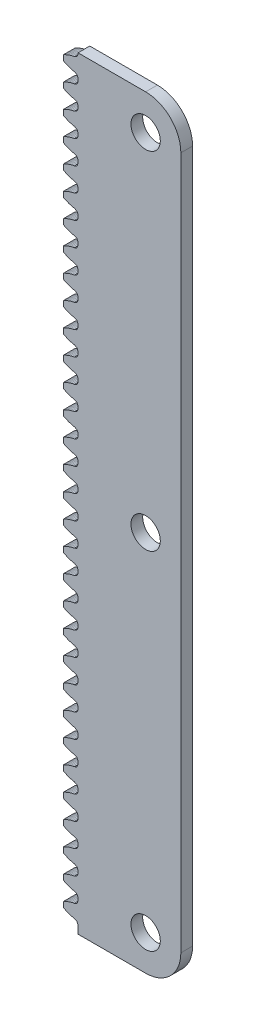
SolidWorks part; units mm, degrees
ref_plane "Спереди" through (0, 0, 0) normal (0, 0, 1) x (1, 0, 0)
ref_plane "Сверху" through (0, 0, 0) normal (0, 1, 0) x (1, 0, 0)
ref_plane "Справа" through (0, 0, 0) normal (1, 0, 0) x (0, 0, -1)
sketch "Эскиз1" plane through (0, 0, 0) normal (0, 0, 1) x (1, 0, 0)
  line L1 (-17.5787, 49.8917) -> (2.4213, 49.8917)
  line L2 (-17.5787, 49.8917) -> (-17.5787, -80.1083)
  line L3 (-17.5787, -80.1083) -> (2.4213, -80.1083)
  line L4 (2.4213, 49.8917) -> (2.4213, -80.1083)
  dimension "D1" = 130
  dimension "D2" = 20
sheet metal parameters "Листовой металл1" thickness 2 parameters "D1"=1.1, "Толщина"=2
base flange "Базовая кромка1" sketch "Эскиз1" thickness 2 reverse thickness direction no parameters "D1"=1.1
fillet "Скругление1" radius 6 2 edges at (2.4213, -80.1083, -1) (2.4213, 49.8917, -1)
sketch "Эскиз4" plane through (0, 0, 0) normal (0, 0, 1) x (1, 0, 0)
  line L0 (-3.5787, 43.8917) -> (-3.5787, -74.1083) construction
  line L1 (-17.5787, -15.1083) -> (2.4213, -15.1083) construction
  line L2 (-17.5787, 49.8917) -> (-17.5787, -80.1083) construction
  line L3 (2.4213, -74.1083) -> (2.4213, 43.8917) construction
  circle A0 centre (-3.5787, -15.1083) radius 2.5
  circle A1 centre (-3.5787, 43.8917) radius 2.5
  circle A2 centre (-3.5787, -74.1083) radius 2.5
  dimension "D1" = 5
  dimension "D2" = 5
  dimension "D3" = 5
extrude "Вырез-Вытянуть1" cut sketch "Эскиз4" against normal blind 10 normal cut yes
sketch "Эскиз5" plane through (0, 0, -2) normal (0, 0, -1) x (-1, 0, 0)
  line L0 (15.1379, 49.5364) -> (15.2757, 49.235)
  line L1 (15.2757, 49.235) -> (15.7076, 49.0269)
  line L2 (15.7076, 49.0269) -> (16.0187, 48.968)
  line L3 (16.0187, 48.968) -> (16.3309, 48.8851)
  line L4 (16.3309, 48.8851) -> (16.6436, 48.7814)
  line L5 (16.6436, 48.7814) -> (16.9562, 48.6588)
  line L6 (16.9562, 48.6588) -> (17.2684, 48.5186)
  line L7 (17.2684, 48.5186) -> (17.5796, 48.3616)
  line L8 (17.5796, 48.3616) -> (17.5796, 47.4619)
  line L9 (17.5796, 47.4619) -> (17.2684, 47.3049)
  line L10 (17.2684, 47.3049) -> (16.9562, 47.1647)
  line L11 (16.9562, 47.1647) -> (16.6436, 47.0421)
  line L12 (16.6436, 47.0421) -> (16.3309, 46.9384)
  line L13 (16.3309, 46.9384) -> (16.0187, 46.8555)
  line L14 (16.0187, 46.8555) -> (15.7076, 46.7967)
  line L15 (15.7076, 46.7967) -> (15.2757, 46.5886)
  line L16 (15.2757, 46.5886) -> (15.1379, 46.2872)
  line L17 (15.1379, 46.2872) -> (15.0887, 45.8974)
  line L18 (15.1379, 45.5076) -> (15.2757, 45.2062)
  line L19 (15.2757, 45.2062) -> (15.7076, 44.9981)
  line L20 (15.7076, 44.9981) -> (16.0187, 44.9393)
  line L21 (16.3309, 44.8564) -> (16.6436, 44.7527)
  line L22 (16.6436, 44.7527) -> (16.9562, 44.6301)
  line L23 (16.9562, 44.6301) -> (17.2684, 44.4899)
  line L24 (17.2684, 44.4899) -> (17.5796, 44.3329)
  line L25 (17.5796, 43.4332) -> (17.2684, 43.2762)
  line L26 (17.2684, 43.2762) -> (16.9562, 43.136)
  line L27 (16.9562, 43.136) -> (16.6436, 43.0134)
  line L28 (16.6436, 43.0134) -> (16.3309, 42.9097)
  line L29 (16.3309, 42.9097) -> (16.0187, 42.8268)
  line L30 (16.0187, 42.8268) -> (15.7076, 42.7679)
  line L31 (15.7076, 42.7679) -> (15.2757, 42.5599)
  line L32 (15.2757, 42.5599) -> (15.1379, 42.2584)
  line L33 (15.1379, 42.2584) -> (15.0887, 41.8687)
  line L34 (15.0887, 45.8974) -> (15.1379, 45.5076)
  line L35 (16.0187, 44.9393) -> (16.3309, 44.8564)
  line L36 (17.5796, 44.3329) -> (17.5796, 43.4332)
  line L37 (15.1379, 41.4789) -> (15.2757, 41.1775)
  line L38 (15.2757, 41.1775) -> (15.7076, 40.9694)
  line L39 (15.7076, 40.9694) -> (16.0187, 40.9106)
  line L40 (16.3309, 40.8276) -> (16.6436, 40.7239)
  line L41 (16.6436, 40.7239) -> (16.9562, 40.6014)
  line L42 (16.9562, 40.6014) -> (17.2684, 40.4611)
  line L43 (17.2684, 40.4611) -> (17.5796, 40.3041)
  line L44 (17.5796, 39.4045) -> (17.2684, 39.2475)
  line L45 (17.2684, 39.2475) -> (16.9562, 39.1072)
  line L46 (16.9562, 39.1072) -> (16.6436, 38.9847)
  line L47 (16.6436, 38.9847) -> (16.3309, 38.881)
  line L48 (16.3309, 38.881) -> (16.0187, 38.798)
  line L49 (16.0187, 38.798) -> (15.7076, 38.7392)
  line L50 (15.7076, 38.7392) -> (15.2757, 38.5311)
  line L51 (15.2757, 38.5311) -> (15.1379, 38.2297)
  line L52 (15.1379, 38.2297) -> (15.0887, 37.8399)
  line L53 (15.0887, 41.8687) -> (15.1379, 41.4789)
  line L54 (16.0187, 40.9106) -> (16.3309, 40.8276)
  line L55 (17.5796, 40.3041) -> (17.5796, 39.4045)
  line L56 (15.1379, 37.4502) -> (15.2757, 37.1488)
  line L57 (15.2757, 37.1488) -> (15.7076, 36.9407)
  line L58 (15.7076, 36.9407) -> (16.0187, 36.8818)
  line L59 (16.3309, 36.7989) -> (16.6436, 36.6952)
  line L60 (16.6436, 36.6952) -> (16.9562, 36.5726)
  line L61 (16.9562, 36.5726) -> (17.2684, 36.4324)
  line L62 (17.2684, 36.4324) -> (17.5796, 36.2754)
  line L63 (17.5796, 35.3757) -> (17.2684, 35.2187)
  line L64 (17.2684, 35.2187) -> (16.9562, 35.0785)
  line L65 (16.9562, 35.0785) -> (16.6436, 34.9559)
  line L66 (16.6436, 34.9559) -> (16.3309, 34.8522)
  line L67 (16.3309, 34.8522) -> (16.0187, 34.7693)
  line L68 (16.0187, 34.7693) -> (15.7076, 34.7105)
  line L69 (15.7076, 34.7105) -> (15.2757, 34.5024)
  line L70 (15.2757, 34.5024) -> (15.1379, 34.201)
  line L71 (15.1379, 34.201) -> (15.0887, 33.8112)
  line L72 (15.0887, 37.8399) -> (15.1379, 37.4502)
  line L73 (16.0187, 36.8818) -> (16.3309, 36.7989)
  line L74 (17.5796, 36.2754) -> (17.5796, 35.3757)
  line L75 (15.1379, 33.4214) -> (15.2757, 33.12)
  line L76 (15.2757, 33.12) -> (15.7076, 32.9119)
  line L77 (15.7076, 32.9119) -> (16.0187, 32.8531)
  line L78 (16.3309, 32.7702) -> (16.6436, 32.6665)
  line L79 (16.6436, 32.6665) -> (16.9562, 32.5439)
  line L80 (16.9562, 32.5439) -> (17.2684, 32.4037)
  line L81 (17.2684, 32.4037) -> (17.5796, 32.2467)
  line L82 (17.5796, 31.347) -> (17.2684, 31.19)
  line L83 (17.2684, 31.19) -> (16.9562, 31.0498)
  line L84 (16.9562, 31.0498) -> (16.6436, 30.9272)
  line L85 (16.6436, 30.9272) -> (16.3309, 30.8235)
  line L86 (16.3309, 30.8235) -> (16.0187, 30.7406)
  line L87 (16.0187, 30.7406) -> (15.7076, 30.6817)
  line L88 (15.7076, 30.6817) -> (15.2757, 30.4736)
  line L89 (15.2757, 30.4736) -> (15.1379, 30.1722)
  line L90 (15.1379, 30.1722) -> (15.0887, 29.7825)
  line L91 (15.0887, 33.8112) -> (15.1379, 33.4214)
  line L92 (16.0187, 32.8531) -> (16.3309, 32.7702)
  line L93 (17.5796, 32.2467) -> (17.5796, 31.347)
  line L94 (15.1379, 29.3927) -> (15.2757, 29.0913)
  line L95 (15.2757, 29.0913) -> (15.7076, 28.8832)
  line L96 (15.7076, 28.8832) -> (16.0187, 28.8244)
  line L97 (16.3309, 28.7414) -> (16.6436, 28.6377)
  line L98 (16.6436, 28.6377) -> (16.9562, 28.5152)
  line L99 (16.9562, 28.5152) -> (17.2684, 28.3749)
  line L100 (17.2684, 28.3749) -> (17.5796, 28.2179)
  line L101 (17.5796, 27.3183) -> (17.2684, 27.1613)
  line L102 (17.2684, 27.1613) -> (16.9562, 27.021)
  line L103 (16.9562, 27.021) -> (16.6436, 26.8985)
  line L104 (16.6436, 26.8985) -> (16.3309, 26.7948)
  line L105 (16.3309, 26.7948) -> (16.0187, 26.7118)
  line L106 (16.0187, 26.7118) -> (15.7076, 26.653)
  line L107 (15.7076, 26.653) -> (15.2757, 26.4449)
  line L108 (15.2757, 26.4449) -> (15.1379, 26.1435)
  line L109 (15.1379, 26.1435) -> (15.0887, 25.7537)
  line L110 (15.0887, 29.7825) -> (15.1379, 29.3927)
  line L111 (16.0187, 28.8244) -> (16.3309, 28.7414)
  line L112 (17.5796, 28.2179) -> (17.5796, 27.3183)
  line L113 (15.1379, 25.364) -> (15.2757, 25.0625)
  line L114 (15.2757, 25.0625) -> (15.7076, 24.8545)
  line L115 (15.7076, 24.8545) -> (16.0187, 24.7956)
  line L116 (16.3309, 24.7127) -> (16.6436, 24.609)
  line L117 (16.6436, 24.609) -> (16.9562, 24.4864)
  line L118 (16.9562, 24.4864) -> (17.2684, 24.3462)
  line L119 (17.2684, 24.3462) -> (17.5796, 24.1892)
  line L120 (17.5796, 23.2895) -> (17.2684, 23.1325)
  line L121 (17.2684, 23.1325) -> (16.9562, 22.9923)
  line L122 (16.9562, 22.9923) -> (16.6436, 22.8697)
  line L123 (16.6436, 22.8697) -> (16.3309, 22.766)
  line L124 (16.3309, 22.766) -> (16.0187, 22.6831)
  line L125 (16.0187, 22.6831) -> (15.7076, 22.6243)
  line L126 (15.7076, 22.6243) -> (15.2757, 22.4162)
  line L127 (15.2757, 22.4162) -> (15.1379, 22.1148)
  line L128 (15.1379, 22.1148) -> (15.0887, 21.725)
  line L129 (15.0887, 25.7537) -> (15.1379, 25.364)
  line L130 (16.0187, 24.7956) -> (16.3309, 24.7127)
  line L131 (17.5796, 24.1892) -> (17.5796, 23.2895)
  line L132 (15.1379, 21.3352) -> (15.2757, 21.0338)
  line L133 (15.2757, 21.0338) -> (15.7076, 20.8257)
  line L134 (15.7076, 20.8257) -> (16.0187, 20.7669)
  line L135 (16.3309, 20.6839) -> (16.6436, 20.5803)
  line L136 (16.6436, 20.5803) -> (16.9562, 20.4577)
  line L137 (16.9562, 20.4577) -> (17.2684, 20.3175)
  line L138 (17.2684, 20.3175) -> (17.5796, 20.1605)
  line L139 (17.5796, 19.2608) -> (17.2684, 19.1038)
  line L140 (17.2684, 19.1038) -> (16.9562, 18.9636)
  line L141 (16.9562, 18.9636) -> (16.6436, 18.841)
  line L142 (16.6436, 18.841) -> (16.3309, 18.7373)
  line L143 (16.3309, 18.7373) -> (16.0187, 18.6544)
  line L144 (16.0187, 18.6544) -> (15.7076, 18.5955)
  line L145 (15.7076, 18.5955) -> (15.2757, 18.3874)
  line L146 (15.2757, 18.3874) -> (15.1379, 18.086)
  line L147 (15.1379, 18.086) -> (15.0887, 17.6963)
  line L148 (15.0887, 21.725) -> (15.1379, 21.3352)
  line L149 (16.0187, 20.7669) -> (16.3309, 20.6839)
  line L150 (17.5796, 20.1605) -> (17.5796, 19.2608)
  line L151 (15.1379, 17.3065) -> (15.2757, 17.0051)
  line L152 (15.2757, 17.0051) -> (15.7076, 16.797)
  line L153 (15.7076, 16.797) -> (16.0187, 16.7381)
  line L154 (16.3309, 16.6552) -> (16.6436, 16.5515)
  line L155 (16.6436, 16.5515) -> (16.9562, 16.429)
  line L156 (16.9562, 16.429) -> (17.2684, 16.2887)
  line L157 (17.2684, 16.2887) -> (17.5796, 16.1317)
  line L158 (17.5796, 15.2321) -> (17.2684, 15.075)
  line L159 (17.2684, 15.075) -> (16.9562, 14.9348)
  line L160 (16.9562, 14.9348) -> (16.6436, 14.8123)
  line L161 (16.6436, 14.8123) -> (16.3309, 14.7086)
  line L162 (16.3309, 14.7086) -> (16.0187, 14.6256)
  line L163 (16.0187, 14.6256) -> (15.7076, 14.5668)
  line L164 (15.7076, 14.5668) -> (15.2757, 14.3587)
  line L165 (15.2757, 14.3587) -> (15.1379, 14.0573)
  line L166 (15.1379, 14.0573) -> (15.0887, 13.6675)
  line L167 (15.0887, 17.6963) -> (15.1379, 17.3065)
  line L168 (16.0187, 16.7381) -> (16.3309, 16.6552)
  line L169 (17.5796, 16.1317) -> (17.5796, 15.2321)
  line L170 (15.1379, 13.2778) -> (15.2757, 12.9763)
  line L171 (15.2757, 12.9763) -> (15.7076, 12.7683)
  line L172 (15.7076, 12.7683) -> (16.0187, 12.7094)
  line L173 (16.3309, 12.6265) -> (16.6436, 12.5228)
  line L174 (16.6436, 12.5228) -> (16.9562, 12.4002)
  line L175 (16.9562, 12.4002) -> (17.2684, 12.26)
  line L176 (17.2684, 12.26) -> (17.5796, 12.103)
  line L177 (17.5796, 11.2033) -> (17.2684, 11.0463)
  line L178 (17.2684, 11.0463) -> (16.9562, 10.9061)
  line L179 (16.9562, 10.9061) -> (16.6436, 10.7835)
  line L180 (16.6436, 10.7835) -> (16.3309, 10.6798)
  line L181 (16.3309, 10.6798) -> (16.0187, 10.5969)
  line L182 (16.0187, 10.5969) -> (15.7076, 10.538)
  line L183 (15.7076, 10.538) -> (15.2757, 10.33)
  line L184 (15.2757, 10.33) -> (15.1379, 10.0286)
  line L185 (15.1379, 10.0286) -> (15.0887, 9.6388)
  line L186 (15.0887, 13.6675) -> (15.1379, 13.2778)
  line L187 (16.0187, 12.7094) -> (16.3309, 12.6265)
  line L188 (17.5796, 12.103) -> (17.5796, 11.2033)
  line L189 (15.1379, 9.249) -> (15.2757, 8.9476)
  line L190 (15.2757, 8.9476) -> (15.7076, 8.7395)
  line L191 (15.7076, 8.7395) -> (16.0187, 8.6807)
  line L192 (16.3309, 8.5977) -> (16.6436, 8.4941)
  line L193 (16.6436, 8.4941) -> (16.9562, 8.3715)
  line L194 (16.9562, 8.3715) -> (17.2684, 8.2313)
  line L195 (17.2684, 8.2313) -> (17.5796, 8.0743)
  line L196 (17.5796, 7.1746) -> (17.2684, 7.0176)
  line L197 (17.2684, 7.0176) -> (16.9562, 6.8774)
  line L198 (16.9562, 6.8774) -> (16.6436, 6.7548)
  line L199 (16.6436, 6.7548) -> (16.3309, 6.6511)
  line L200 (16.3309, 6.6511) -> (16.0187, 6.5682)
  line L201 (16.0187, 6.5682) -> (15.7076, 6.5093)
  line L202 (15.7076, 6.5093) -> (15.2757, 6.3012)
  line L203 (15.2757, 6.3012) -> (15.1379, 5.9998)
  line L204 (15.1379, 5.9998) -> (15.0887, 5.6101)
  line L205 (15.0887, 9.6388) -> (15.1379, 9.249)
  line L206 (16.0187, 8.6807) -> (16.3309, 8.5977)
  line L207 (17.5796, 8.0743) -> (17.5796, 7.1746)
  line L208 (15.1379, 5.2203) -> (15.2757, 4.9189)
  line L209 (15.2757, 4.9189) -> (15.7076, 4.7108)
  line L210 (15.7076, 4.7108) -> (16.0187, 4.6519)
  line L211 (16.3309, 4.569) -> (16.6436, 4.4653)
  line L212 (16.6436, 4.4653) -> (16.9562, 4.3427)
  line L213 (16.9562, 4.3427) -> (17.2684, 4.2025)
  line L214 (17.2684, 4.2025) -> (17.5796, 4.0455)
  line L215 (17.5796, 3.1458) -> (17.2684, 2.9888)
  line L216 (17.2684, 2.9888) -> (16.9562, 2.8486)
  line L217 (16.9562, 2.8486) -> (16.6436, 2.7261)
  line L218 (16.6436, 2.7261) -> (16.3309, 2.6224)
  line L219 (16.3309, 2.6224) -> (16.0187, 2.5394)
  line L220 (16.0187, 2.5394) -> (15.7076, 2.4806)
  line L221 (15.7076, 2.4806) -> (15.2757, 2.2725)
  line L222 (15.2757, 2.2725) -> (15.1379, 1.9711)
  line L223 (15.1379, 1.9711) -> (15.0887, 1.5813)
  line L224 (15.0887, 5.6101) -> (15.1379, 5.2203)
  line L225 (16.0187, 4.6519) -> (16.3309, 4.569)
  line L226 (17.5796, 4.0455) -> (17.5796, 3.1458)
  line L227 (15.1379, 1.1916) -> (15.2757, 0.8901)
  line L228 (15.2757, 0.8901) -> (15.7076, 0.6821)
  line L229 (15.7076, 0.6821) -> (16.0187, 0.6232)
  line L230 (16.3309, 0.5403) -> (16.6436, 0.4366)
  line L231 (16.6436, 0.4366) -> (16.9562, 0.314)
  line L232 (16.9562, 0.314) -> (17.2684, 0.1738)
  line L233 (17.2684, 0.1738) -> (17.5796, 0.0168)
  line L234 (17.5796, -0.8829) -> (17.2684, -1.0399)
  line L235 (17.2684, -1.0399) -> (16.9562, -1.1801)
  line L236 (16.9562, -1.1801) -> (16.6436, -1.3027)
  line L237 (16.6436, -1.3027) -> (16.3309, -1.4064)
  line L238 (16.3309, -1.4064) -> (16.0187, -1.4893)
  line L239 (16.0187, -1.4893) -> (15.7076, -1.5482)
  line L240 (15.7076, -1.5482) -> (15.2757, -1.7562)
  line L241 (15.2757, -1.7562) -> (15.1379, -2.0577)
  line L242 (15.1379, -2.0577) -> (15.0887, -2.4474)
  line L243 (15.0887, 1.5813) -> (15.1379, 1.1916)
  line L244 (16.0187, 0.6232) -> (16.3309, 0.5403)
  line L245 (17.5796, 0.0168) -> (17.5796, -0.8829)
  line L246 (15.1379, -2.8372) -> (15.2757, -3.1386)
  line L247 (15.2757, -3.1386) -> (15.7076, -3.3467)
  line L248 (15.7076, -3.3467) -> (16.0187, -3.4055)
  line L249 (16.3309, -3.4885) -> (16.6436, -3.5922)
  line L250 (16.6436, -3.5922) -> (16.9562, -3.7147)
  line L251 (16.9562, -3.7147) -> (17.2684, -3.8549)
  line L252 (17.2684, -3.8549) -> (17.5796, -4.012)
  line L253 (17.5796, -4.9116) -> (17.2684, -5.0686)
  line L254 (17.2684, -5.0686) -> (16.9562, -5.2089)
  line L255 (16.9562, -5.2089) -> (16.6436, -5.3314)
  line L256 (16.6436, -5.3314) -> (16.3309, -5.4351)
  line L257 (16.3309, -5.4351) -> (16.0187, -5.518)
  line L258 (16.0187, -5.518) -> (15.7076, -5.5769)
  line L259 (15.7076, -5.5769) -> (15.2757, -5.785)
  line L260 (15.2757, -5.785) -> (15.1379, -6.0864)
  line L261 (15.1379, -6.0864) -> (15.0887, -6.4762)
  line L262 (15.0887, -2.4474) -> (15.1379, -2.8372)
  line L263 (16.0187, -3.4055) -> (16.3309, -3.4885)
  line L264 (17.5796, -4.012) -> (17.5796, -4.9116)
  line L265 (15.1379, -6.8659) -> (15.2757, -7.1673)
  line L266 (15.2757, -7.1673) -> (15.7076, -7.3754)
  line L267 (15.7076, -7.3754) -> (16.0187, -7.4343)
  line L268 (16.3309, -7.5172) -> (16.6436, -7.6209)
  line L269 (16.6436, -7.6209) -> (16.9562, -7.7435)
  line L270 (16.9562, -7.7435) -> (17.2684, -7.8837)
  line L271 (17.2684, -7.8837) -> (17.5796, -8.0407)
  line L272 (17.5796, -8.9404) -> (17.2684, -9.0974)
  line L273 (17.2684, -9.0974) -> (16.9562, -9.2376)
  line L274 (16.9562, -9.2376) -> (16.6436, -9.3602)
  line L275 (16.6436, -9.3602) -> (16.3309, -9.4638)
  line L276 (16.3309, -9.4638) -> (16.0187, -9.5468)
  line L277 (16.0187, -9.5468) -> (15.7076, -9.6056)
  line L278 (15.7076, -9.6056) -> (15.2757, -9.8137)
  line L279 (15.2757, -9.8137) -> (15.1379, -10.1151)
  line L280 (15.1379, -10.1151) -> (15.0887, -10.5049)
  line L281 (15.0887, -6.4762) -> (15.1379, -6.8659)
  line L282 (16.0187, -7.4343) -> (16.3309, -7.5172)
  line L283 (17.5796, -8.0407) -> (17.5796, -8.9404)
  line L284 (15.1379, -10.8947) -> (15.2757, -11.1961)
  line L285 (15.2757, -11.1961) -> (15.7076, -11.4042)
  line L286 (15.7076, -11.4042) -> (16.0187, -11.463)
  line L287 (16.3309, -11.5459) -> (16.6436, -11.6496)
  line L288 (16.6436, -11.6496) -> (16.9562, -11.7722)
  line L289 (16.9562, -11.7722) -> (17.2684, -11.9124)
  line L290 (17.2684, -11.9124) -> (17.5796, -12.0694)
  line L291 (17.5796, -12.9691) -> (17.2684, -13.1261)
  line L292 (17.2684, -13.1261) -> (16.9562, -13.2663)
  line L293 (16.9562, -13.2663) -> (16.6436, -13.3889)
  line L294 (16.6436, -13.3889) -> (16.3309, -13.4926)
  line L295 (16.3309, -13.4926) -> (16.0187, -13.5755)
  line L296 (16.0187, -13.5755) -> (15.7076, -13.6344)
  line L297 (15.7076, -13.6344) -> (15.2757, -13.8424)
  line L298 (15.2757, -13.8424) -> (15.1379, -14.1439)
  line L299 (15.1379, -14.1439) -> (15.0887, -14.5336)
  line L300 (15.0887, -10.5049) -> (15.1379, -10.8947)
  line L301 (16.0187, -11.463) -> (16.3309, -11.5459)
  line L302 (17.5796, -12.0694) -> (17.5796, -12.9691)
  line L303 (15.1379, -14.9234) -> (15.2757, -15.2248)
  line L304 (15.2757, -15.2248) -> (15.7076, -15.4329)
  line L305 (15.7076, -15.4329) -> (16.0187, -15.4917)
  line L306 (16.3309, -15.5747) -> (16.6436, -15.6784)
  line L307 (16.6436, -15.6784) -> (16.9562, -15.8009)
  line L308 (16.9562, -15.8009) -> (17.2684, -15.9411)
  line L309 (17.2684, -15.9411) -> (17.5796, -16.0982)
  line L310 (17.5796, -16.9978) -> (17.2684, -17.1548)
  line L311 (17.2684, -17.1548) -> (16.9562, -17.2951)
  line L312 (16.9562, -17.2951) -> (16.6436, -17.4176)
  line L313 (16.6436, -17.4176) -> (16.3309, -17.5213)
  line L314 (16.3309, -17.5213) -> (16.0187, -17.6043)
  line L315 (16.0187, -17.6043) -> (15.7076, -17.6631)
  line L316 (15.7076, -17.6631) -> (15.2757, -17.8712)
  line L317 (15.2757, -17.8712) -> (15.1379, -18.1726)
  line L318 (15.1379, -18.1726) -> (15.0887, -18.5624)
  line L319 (15.0887, -14.5336) -> (15.1379, -14.9234)
  line L320 (16.0187, -15.4917) -> (16.3309, -15.5747)
  line L321 (17.5796, -16.0982) -> (17.5796, -16.9978)
  line L322 (15.1379, -18.9521) -> (15.2757, -19.2535)
  line L323 (15.2757, -19.2535) -> (15.7076, -19.4616)
  line L324 (15.7076, -19.4616) -> (16.0187, -19.5205)
  line L325 (16.3309, -19.6034) -> (16.6436, -19.7071)
  line L326 (16.6436, -19.7071) -> (16.9562, -19.8297)
  line L327 (16.9562, -19.8297) -> (17.2684, -19.9699)
  line L328 (17.2684, -19.9699) -> (17.5796, -20.1269)
  line L329 (17.5796, -21.0266) -> (17.2684, -21.1836)
  line L330 (17.2684, -21.1836) -> (16.9562, -21.3238)
  line L331 (16.9562, -21.3238) -> (16.6436, -21.4464)
  line L332 (16.6436, -21.4464) -> (16.3309, -21.5501)
  line L333 (16.3309, -21.5501) -> (16.0187, -21.633)
  line L334 (16.0187, -21.633) -> (15.7076, -21.6918)
  line L335 (15.7076, -21.6918) -> (15.2757, -21.8999)
  line L336 (15.2757, -21.8999) -> (15.1379, -22.2013)
  line L337 (15.1379, -22.2013) -> (15.0887, -22.5911)
  line L338 (15.0887, -18.5624) -> (15.1379, -18.9521)
  line L339 (16.0187, -19.5205) -> (16.3309, -19.6034)
  line L340 (17.5796, -20.1269) -> (17.5796, -21.0266)
  line L341 (15.1379, -22.9809) -> (15.2757, -23.2823)
  line L342 (15.2757, -23.2823) -> (15.7076, -23.4904)
  line L343 (15.7076, -23.4904) -> (16.0187, -23.5492)
  line L344 (16.3309, -23.6321) -> (16.6436, -23.7358)
  line L345 (16.6436, -23.7358) -> (16.9562, -23.8584)
  line L346 (16.9562, -23.8584) -> (17.2684, -23.9986)
  line L347 (17.2684, -23.9986) -> (17.5796, -24.1556)
  line L348 (17.5796, -25.0553) -> (17.2684, -25.2123)
  line L349 (17.2684, -25.2123) -> (16.9562, -25.3525)
  line L350 (16.9562, -25.3525) -> (16.6436, -25.4751)
  line L351 (16.6436, -25.4751) -> (16.3309, -25.5788)
  line L352 (16.3309, -25.5788) -> (16.0187, -25.6617)
  line L353 (16.0187, -25.6617) -> (15.7076, -25.7206)
  line L354 (15.7076, -25.7206) -> (15.2757, -25.9286)
  line L355 (15.2757, -25.9286) -> (15.1379, -26.2301)
  line L356 (15.1379, -26.2301) -> (15.0887, -26.6198)
  line L357 (15.0887, -22.5911) -> (15.1379, -22.9809)
  line L358 (16.0187, -23.5492) -> (16.3309, -23.6321)
  line L359 (17.5796, -24.1556) -> (17.5796, -25.0553)
  line L360 (15.1379, -27.0096) -> (15.2757, -27.311)
  line L361 (15.2757, -27.311) -> (15.7076, -27.5191)
  line L362 (15.7076, -27.5191) -> (16.0187, -27.5779)
  line L363 (16.3309, -27.6609) -> (16.6436, -27.7646)
  line L364 (16.6436, -27.7646) -> (16.9562, -27.8871)
  line L365 (16.9562, -27.8871) -> (17.2684, -28.0274)
  line L366 (17.2684, -28.0274) -> (17.5796, -28.1844)
  line L367 (17.5796, -29.084) -> (17.2684, -29.241)
  line L368 (17.2684, -29.241) -> (16.9562, -29.3813)
  line L369 (16.9562, -29.3813) -> (16.6436, -29.5038)
  line L370 (16.6436, -29.5038) -> (16.3309, -29.6075)
  line L371 (16.3309, -29.6075) -> (16.0187, -29.6905)
  line L372 (16.0187, -29.6905) -> (15.7076, -29.7493)
  line L373 (15.7076, -29.7493) -> (15.2757, -29.9574)
  line L374 (15.2757, -29.9574) -> (15.1379, -30.2588)
  line L375 (15.1379, -30.2588) -> (15.0887, -30.6486)
  line L376 (15.0887, -26.6198) -> (15.1379, -27.0096)
  line L377 (16.0187, -27.5779) -> (16.3309, -27.6609)
  line L378 (17.5796, -28.1844) -> (17.5796, -29.084)
  line L379 (15.1379, -31.0383) -> (15.2757, -31.3397)
  line L380 (15.2757, -31.3397) -> (15.7076, -31.5478)
  line L381 (15.7076, -31.5478) -> (16.0187, -31.6067)
  line L382 (16.3309, -31.6896) -> (16.6436, -31.7933)
  line L383 (16.6436, -31.7933) -> (16.9562, -31.9159)
  line L384 (16.9562, -31.9159) -> (17.2684, -32.0561)
  line L385 (17.2684, -32.0561) -> (17.5796, -32.2131)
  line L386 (17.5796, -33.1128) -> (17.2684, -33.2698)
  line L387 (17.2684, -33.2698) -> (16.9562, -33.41)
  line L388 (16.9562, -33.41) -> (16.6436, -33.5326)
  line L389 (16.6436, -33.5326) -> (16.3309, -33.6363)
  line L390 (16.3309, -33.6363) -> (16.0187, -33.7192)
  line L391 (16.0187, -33.7192) -> (15.7076, -33.778)
  line L392 (15.7076, -33.778) -> (15.2757, -33.9861)
  line L393 (15.2757, -33.9861) -> (15.1379, -34.2875)
  line L394 (15.1379, -34.2875) -> (15.0887, -34.6773)
  line L395 (15.0887, -30.6486) -> (15.1379, -31.0383)
  line L396 (16.0187, -31.6067) -> (16.3309, -31.6896)
  line L397 (17.5796, -32.2131) -> (17.5796, -33.1128)
  line L398 (15.1379, -35.0671) -> (15.2757, -35.3685)
  line L399 (15.2757, -35.3685) -> (15.7076, -35.5766)
  line L400 (15.7076, -35.5766) -> (16.0187, -35.6354)
  line L401 (16.3309, -35.7183) -> (16.6436, -35.822)
  line L402 (16.6436, -35.822) -> (16.9562, -35.9446)
  line L403 (16.9562, -35.9446) -> (17.2684, -36.0848)
  line L404 (17.2684, -36.0848) -> (17.5796, -36.2418)
  line L405 (17.5796, -37.1415) -> (17.2684, -37.2985)
  line L406 (17.2684, -37.2985) -> (16.9562, -37.4387)
  line L407 (16.9562, -37.4387) -> (16.6436, -37.5613)
  line L408 (16.6436, -37.5613) -> (16.3309, -37.665)
  line L409 (16.3309, -37.665) -> (16.0187, -37.7479)
  line L410 (16.0187, -37.7479) -> (15.7076, -37.8068)
  line L411 (15.7076, -37.8068) -> (15.2757, -38.0149)
  line L412 (15.2757, -38.0149) -> (15.1379, -38.3163)
  line L413 (15.1379, -38.3163) -> (15.0887, -38.706)
  line L414 (15.0887, -34.6773) -> (15.1379, -35.0671)
  line L415 (16.0187, -35.6354) -> (16.3309, -35.7183)
  line L416 (17.5796, -36.2418) -> (17.5796, -37.1415)
  line L417 (15.1379, -39.0958) -> (15.2757, -39.3972)
  line L418 (15.2757, -39.3972) -> (15.7076, -39.6053)
  line L419 (15.7076, -39.6053) -> (16.0187, -39.6641)
  line L420 (16.3309, -39.7471) -> (16.6436, -39.8508)
  line L421 (16.6436, -39.8508) -> (16.9562, -39.9733)
  line L422 (16.9562, -39.9733) -> (17.2684, -40.1136)
  line L423 (17.2684, -40.1136) -> (17.5796, -40.2706)
  line L424 (17.5796, -41.1702) -> (17.2684, -41.3273)
  line L425 (17.2684, -41.3273) -> (16.9562, -41.4675)
  line L426 (16.9562, -41.4675) -> (16.6436, -41.59)
  line L427 (16.6436, -41.59) -> (16.3309, -41.6937)
  line L428 (16.3309, -41.6937) -> (16.0187, -41.7767)
  line L429 (16.0187, -41.7767) -> (15.7076, -41.8355)
  line L430 (15.7076, -41.8355) -> (15.2757, -42.0436)
  line L431 (15.2757, -42.0436) -> (15.1379, -42.345)
  line L432 (15.1379, -42.345) -> (15.0887, -42.7348)
  line L433 (15.0887, -38.706) -> (15.1379, -39.0958)
  line L434 (16.0187, -39.6641) -> (16.3309, -39.7471)
  line L435 (17.5796, -40.2706) -> (17.5796, -41.1702)
  line L436 (15.1379, -43.1245) -> (15.2757, -43.426)
  line L437 (15.2757, -43.426) -> (15.7076, -43.634)
  line L438 (15.7076, -43.634) -> (16.0187, -43.6929)
  line L439 (16.3309, -43.7758) -> (16.6436, -43.8795)
  line L440 (16.6436, -43.8795) -> (16.9562, -44.0021)
  line L441 (16.9562, -44.0021) -> (17.2684, -44.1423)
  line L442 (17.2684, -44.1423) -> (17.5796, -44.2993)
  line L443 (17.5796, -45.199) -> (17.2684, -45.356)
  line L444 (17.2684, -45.356) -> (16.9562, -45.4962)
  line L445 (16.9562, -45.4962) -> (16.6436, -45.6188)
  line L446 (16.6436, -45.6188) -> (16.3309, -45.7225)
  line L447 (16.3309, -45.7225) -> (16.0187, -45.8054)
  line L448 (16.0187, -45.8054) -> (15.7076, -45.8642)
  line L449 (15.0887, 49.9261) -> (15.1379, 49.5364)
  line L450 (15.7076, -45.8642) -> (15.2757, -46.0723)
  line L451 (15.2757, -46.0723) -> (15.1379, -46.3737)
  line L452 (15.1379, -46.3737) -> (15.0887, -46.7635)
  line L453 (15.0887, -42.7348) -> (15.1379, -43.1245)
  line L454 (16.0187, -43.6929) -> (16.3309, -43.7758)
  line L455 (17.5796, -44.2993) -> (17.5796, -45.199)
  line L456 (15.1379, -47.1533) -> (15.2757, -47.4547)
  line L457 (15.2757, -47.4547) -> (15.7076, -47.6628)
  line L458 (15.7076, -47.6628) -> (16.0187, -47.7216)
  line L459 (16.3309, -47.8046) -> (16.6436, -47.9082)
  line L460 (16.6436, -47.9082) -> (16.9562, -48.0308)
  line L461 (16.9562, -48.0308) -> (17.2684, -48.171)
  line L462 (17.2684, -48.171) -> (17.5796, -48.328)
  line L463 (17.5796, -49.2277) -> (17.2684, -49.3847)
  line L464 (17.2684, -49.3847) -> (16.9562, -49.5249)
  line L465 (16.9562, -49.5249) -> (16.6436, -49.6475)
  line L466 (16.6436, -49.6475) -> (16.3309, -49.7512)
  line L467 (16.3309, -49.7512) -> (16.0187, -49.8341)
  line L468 (16.0187, -49.8341) -> (15.7076, -49.893)
  line L469 (15.7076, -49.893) -> (15.2757, -50.1011)
  line L470 (15.2757, -50.1011) -> (15.1379, -50.4025)
  line L471 (15.1379, -50.4025) -> (15.0887, -50.7922)
  line L472 (15.0887, -46.7635) -> (15.1379, -47.1533)
  line L473 (16.0187, -47.7216) -> (16.3309, -47.8046)
  line L474 (17.5796, -48.328) -> (17.5796, -49.2277)
  line L475 (15.1379, -51.182) -> (15.2757, -51.4834)
  line L476 (15.2757, -51.4834) -> (15.7076, -51.6915)
  line L477 (15.7076, -51.6915) -> (16.0187, -51.7504)
  line L478 (16.3309, -51.8333) -> (16.6436, -51.937)
  line L479 (16.6436, -51.937) -> (16.9562, -52.0595)
  line L480 (16.9562, -52.0595) -> (17.2684, -52.1998)
  line L481 (17.2684, -52.1998) -> (17.5796, -52.3568)
  line L482 (17.5796, -53.2564) -> (17.2684, -53.4135)
  line L483 (17.2684, -53.4135) -> (16.9562, -53.5537)
  line L484 (16.9562, -53.5537) -> (16.6436, -53.6762)
  line L485 (16.6436, -53.6762) -> (16.3309, -53.7799)
  line L486 (16.3309, -53.7799) -> (16.0187, -53.8629)
  line L487 (16.0187, -53.8629) -> (15.7076, -53.9217)
  line L488 (15.7076, -53.9217) -> (15.2757, -54.1298)
  line L489 (15.2757, -54.1298) -> (15.1379, -54.4312)
  line L490 (15.1379, -54.4312) -> (15.0887, -54.821)
  line L491 (15.0887, -50.7922) -> (15.1379, -51.182)
  line L492 (16.0187, -51.7504) -> (16.3309, -51.8333)
  line L493 (17.5796, -52.3568) -> (17.5796, -53.2564)
  line L494 (15.1379, -55.2107) -> (15.2757, -55.5122)
  line L495 (15.2757, -55.5122) -> (15.7076, -55.7202)
  line L496 (15.7076, -55.7202) -> (16.0187, -55.7791)
  line L497 (16.3309, -55.862) -> (16.6436, -55.9657)
  line L498 (16.6436, -55.9657) -> (16.9562, -56.0883)
  line L499 (16.9562, -56.0883) -> (17.2684, -56.2285)
  line L500 (17.2684, -56.2285) -> (17.5796, -56.3855)
  line L501 (17.5796, -57.2852) -> (17.2684, -57.4422)
  line L502 (17.2684, -57.4422) -> (16.9562, -57.5824)
  line L503 (16.9562, -57.5824) -> (16.6436, -57.705)
  line L504 (16.6436, -57.705) -> (16.3309, -57.8087)
  line L505 (16.3309, -57.8087) -> (16.0187, -57.8916)
  line L506 (16.0187, -57.8916) -> (15.7076, -57.9505)
  line L507 (15.7076, -57.9505) -> (15.2757, -58.1585)
  line L508 (15.2757, -58.1585) -> (15.1379, -58.46)
  line L509 (15.1379, -58.46) -> (15.0887, -58.8497)
  line L510 (15.0887, -54.821) -> (15.1379, -55.2107)
  line L511 (16.0187, -55.7791) -> (16.3309, -55.862)
  line L512 (17.5796, -56.3855) -> (17.5796, -57.2852)
  line L513 (15.1379, -59.2395) -> (15.2757, -59.5409)
  line L514 (15.2757, -59.5409) -> (15.7076, -59.749)
  line L515 (15.7076, -59.749) -> (16.0187, -59.8078)
  line L516 (16.3309, -59.8908) -> (16.6436, -59.9944)
  line L517 (16.6436, -59.9944) -> (16.9562, -60.117)
  line L518 (16.9562, -60.117) -> (17.2684, -60.2572)
  line L519 (17.2684, -60.2572) -> (17.5796, -60.4142)
  line L520 (17.5796, -61.3139) -> (17.2684, -61.4709)
  line L521 (17.2684, -61.4709) -> (16.9562, -61.6111)
  line L522 (16.9562, -61.6111) -> (16.6436, -61.7337)
  line L523 (16.6436, -61.7337) -> (16.3309, -61.8374)
  line L524 (16.3309, -61.8374) -> (16.0187, -61.9203)
  line L525 (16.0187, -61.9203) -> (15.7076, -61.9792)
  line L526 (15.7076, -61.9792) -> (15.2757, -62.1873)
  line L527 (15.2757, -62.1873) -> (15.1379, -62.4887)
  line L528 (15.1379, -62.4887) -> (15.0887, -62.8785)
  line L529 (15.0887, -58.8497) -> (15.1379, -59.2395)
  line L530 (16.0187, -59.8078) -> (16.3309, -59.8908)
  line L531 (17.5796, -60.4142) -> (17.5796, -61.3139)
  line L532 (15.1379, -63.2682) -> (15.2757, -63.5696)
  line L533 (15.2757, -63.5696) -> (15.7076, -63.7777)
  line L534 (15.7076, -63.7777) -> (16.0187, -63.8366)
  line L535 (16.3309, -63.9195) -> (16.6436, -64.0232)
  line L536 (16.6436, -64.0232) -> (16.9562, -64.1458)
  line L537 (16.9562, -64.1458) -> (17.2684, -64.286)
  line L538 (17.2684, -64.286) -> (17.5796, -64.443)
  line L539 (17.5796, -65.3427) -> (17.2684, -65.4997)
  line L540 (17.2684, -65.4997) -> (16.9562, -65.6399)
  line L541 (16.9562, -65.6399) -> (16.6436, -65.7625)
  line L542 (16.6436, -65.7625) -> (16.3309, -65.8661)
  line L543 (16.3309, -65.8661) -> (16.0187, -65.9491)
  line L544 (16.0187, -65.9491) -> (15.7076, -66.0079)
  line L545 (15.7076, -66.0079) -> (15.2757, -66.216)
  line L546 (15.2757, -66.216) -> (15.1379, -66.5174)
  line L547 (15.1379, -66.5174) -> (15.0887, -66.9072)
  line L548 (15.0887, -62.8785) -> (15.1379, -63.2682)
  line L549 (16.0187, -63.8366) -> (16.3309, -63.9195)
  line L550 (17.5796, -64.443) -> (17.5796, -65.3427)
  line L551 (15.1379, -67.2969) -> (15.2757, -67.5984)
  line L552 (15.2757, -67.5984) -> (15.7076, -67.8064)
  line L553 (15.7076, -67.8064) -> (16.0187, -67.8653)
  line L554 (16.3309, -67.9482) -> (16.6436, -68.0519)
  line L555 (16.6436, -68.0519) -> (16.9562, -68.1745)
  line L556 (16.9562, -68.1745) -> (17.2684, -68.3147)
  line L557 (17.2684, -68.3147) -> (17.5796, -68.4717)
  line L558 (17.5796, -69.3714) -> (17.2684, -69.5284)
  line L559 (17.2684, -69.5284) -> (16.9562, -69.6686)
  line L560 (16.9562, -69.6686) -> (16.6436, -69.7912)
  line L561 (16.6436, -69.7912) -> (16.3309, -69.8949)
  line L562 (16.3309, -69.8949) -> (16.0187, -69.9778)
  line L563 (16.0187, -69.9778) -> (15.7076, -70.0367)
  line L564 (15.7076, -70.0367) -> (15.2757, -70.2447)
  line L565 (15.2757, -70.2447) -> (15.1379, -70.5462)
  line L566 (15.1379, -70.5462) -> (15.0887, -70.9359)
  line L567 (15.0887, -66.9072) -> (15.1379, -67.2969)
  line L568 (16.0187, -67.8653) -> (16.3309, -67.9482)
  line L569 (17.5796, -68.4717) -> (17.5796, -69.3714)
  line L570 (15.1379, -71.3257) -> (15.2757, -71.6271)
  line L571 (15.2757, -71.6271) -> (15.7076, -71.8352)
  line L572 (15.7076, -71.8352) -> (16.0187, -71.894)
  line L573 (16.3309, -71.977) -> (16.6436, -72.0807)
  line L574 (16.6436, -72.0807) -> (16.9562, -72.2032)
  line L575 (16.9562, -72.2032) -> (17.2684, -72.3434)
  line L576 (17.2684, -72.3434) -> (17.5796, -72.5005)
  line L577 (17.5796, -73.4001) -> (17.2684, -73.5571)
  line L578 (17.2684, -73.5571) -> (16.9562, -73.6974)
  line L579 (16.9562, -73.6974) -> (16.6436, -73.8199)
  line L580 (16.6436, -73.8199) -> (16.3309, -73.9236)
  line L581 (16.3309, -73.9236) -> (16.0187, -74.0065)
  line L582 (16.0187, -74.0065) -> (15.7076, -74.0654)
  line L583 (15.7076, -74.0654) -> (15.2757, -74.2735)
  line L584 (15.2757, -74.2735) -> (15.1379, -74.5749)
  line L585 (15.1379, -74.5749) -> (15.0887, -74.9647)
  line L586 (15.0887, -70.9359) -> (15.1379, -71.3257)
  line L587 (16.0187, -71.894) -> (16.3309, -71.977)
  line L588 (17.5796, -72.5005) -> (17.5796, -73.4001)
  line L589 (15.1379, -75.3544) -> (15.2757, -75.6558)
  line L590 (15.2757, -75.6558) -> (15.7076, -75.8639)
  line L591 (15.7076, -75.8639) -> (16.0187, -75.9228)
  line L592 (16.3309, -76.0057) -> (16.6436, -76.1094)
  line L593 (16.6436, -76.1094) -> (16.9562, -76.232)
  line L594 (16.9562, -76.232) -> (17.2684, -76.3722)
  line L595 (17.2684, -76.3722) -> (17.5796, -76.5292)
  line L596 (17.5796, -77.4289) -> (17.2684, -77.5859)
  line L597 (17.2684, -77.5859) -> (16.9562, -77.7261)
  line L598 (16.9562, -77.7261) -> (16.6436, -77.8487)
  line L599 (16.6436, -77.8487) -> (16.3309, -77.9523)
  line L600 (16.3309, -77.9523) -> (16.0187, -78.0353)
  line L601 (16.0187, -78.0353) -> (15.7076, -78.0941)
  line L602 (15.7076, -78.0941) -> (15.2757, -78.3022)
  line L603 (15.2757, -78.3022) -> (15.1379, -78.6036)
  line L604 (15.1379, -78.6036) -> (15.0887, -78.9934)
  line L605 (15.0887, -74.9647) -> (15.1379, -75.3544)
  line L606 (16.0187, -75.9228) -> (16.3309, -76.0057)
  line L607 (17.5796, -76.5292) -> (17.5796, -77.4289)
  line L608 (15.0887, -78.9934) -> (15.0887, -80.2321)
  line L609 (15.0887, -80.2321) -> (18.8529, -80.2321)
  line L610 (18.8529, -80.2321) -> (18.8529, 51.2362)
  line L611 (18.8529, 51.2362) -> (15.0887, 51.2362)
  line L612 (15.0887, 51.2362) -> (15.0887, 49.9261)
  line L627 (15.1379, -79.3832) -> (15.2757, -79.6846) [skipped]
  line L628 (15.2757, -79.6846) -> (15.7076, -79.8927) [skipped]
  line L629 (15.7076, -79.8927) -> (16.0187, -79.9515) [skipped]
  line L630 (16.3309, -80.0344) -> (16.6436, -80.1381) [skipped]
  line L631 (16.6436, -80.1381) -> (16.9562, -80.2607) [skipped]
  line L632 (16.9562, -80.2607) -> (17.2684, -80.4009) [skipped]
  line L633 (17.2684, -80.4009) -> (17.5796, -80.5579) [skipped]
  line L634 (17.5796, -81.4576) -> (17.2684, -81.6146) [skipped]
  line L635 (17.2684, -81.6146) -> (16.9562, -81.7548) [skipped]
  line L636 (16.9562, -81.7548) -> (16.6436, -81.8774) [skipped]
  line L637 (16.6436, -81.8774) -> (16.3309, -81.9811) [skipped]
  line L638 (16.3309, -81.9811) -> (16.0187, -82.064) [skipped]
  line L639 (16.0187, -82.064) -> (15.7076, -82.1229) [skipped]
  line L640 (15.7076, -82.1229) -> (15.2757, -82.3309) [skipped]
  line L641 (15.2757, -82.3309) -> (15.1379, -82.6324) [skipped]
  line L642 (15.1379, -82.6324) -> (15.0887, -83.0221) [skipped]
  line L643 (16.0187, -79.9515) -> (16.3309, -80.0344) [skipped]
  line L644 (17.5796, -80.5579) -> (17.5796, -81.4576) [skipped]
  line L645 (15.0887, -78.9934) -> (15.1379, -79.3832) [skipped]
  dimension "D1" = 33
extrude "Вырез-Вытянуть2" cut sketch "Эскиз5" against normal blind 10 normal cut yes
flat pattern "Развертка1" [suppressed]
sketch "Сгиб-Линии1" plane through (0, 0, 0) normal (0, 1, 0) x (1, 0, 0)
sketch3d "Граничная рамка1" [suppressed]
  line L0 (-2.4213, 49.8917, 0) -> (-2.4213, -80.1083, 0) construction
  line L1 (27.5787, 49.8917, 0) -> (27.5787, -80.1083, 0) construction
  line L2 (-2.4213, 49.8917, 0) -> (27.5787, 49.8917, 0) construction
  line L3 (-2.4213, -80.1083, 0) -> (27.5787, -80.1083, 0) construction
